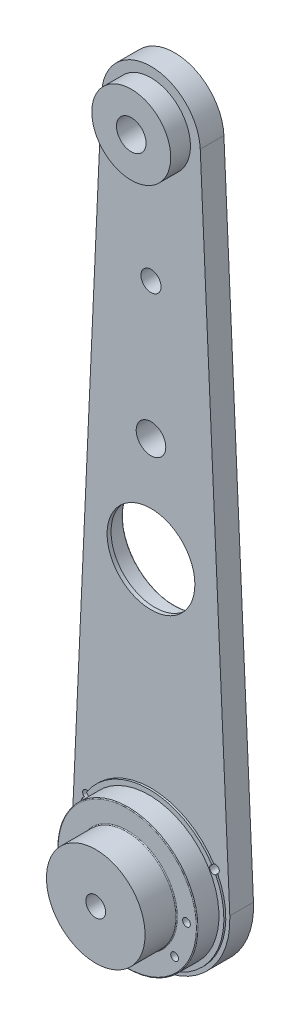
SolidWorks part; units mm, degrees
ref_plane "Front Plane" through (0, 0, 0) normal (0, 0, 1) x (1, 0, 0)
ref_plane "Top Plane" through (0, 0, 0) normal (0, 1, 0) x (1, 0, 0)
ref_plane "Right Plane" through (0, 0, 0) normal (1, 0, 0) x (0, 0, -1)
sketch "Sketch1" plane through (0, 0, 0) normal (0, 0, 1) x (1, 0, 0)
  line L0 (0, 209.417) -> (0, 0) construction
  line L1 (25.3737, 1.1553) -> (15.8586, 210.1391)
  line L2 (-15.8586, 210.1391) -> (-25.3737, 1.1553)
  circle A1 centre (0, 209.417) radius 4.7625
  arc A2 (-15.8586, 210.1391) -> (15.8586, 210.1391) centre (0, 209.417) cw
  arc A3 (-25.3737, 1.1553) -> (25.3737, 1.1553) centre (0, 0) ccw
  dimension "D2" = 15.875
  dimension "D3" = 25.4
  dimension "D4" = 9.525
  dimension "D1" = 209.417
extrude "Boss-Extrude1" add sketch "Sketch1" along normal mid plane 7.62
sketch "Sketch2" plane through (0, 0, 3.81) normal (0, 0, 1) x (1, 0, 0)
  circle A0 centre (0, 0) radius 22.5
  dimension "D1" = 45
extrude "Boss-Extrude2" add sketch "Sketch2" along normal blind 7.62
sketch "Sketch3" plane through (0, 0, 3.81) normal (0, 0, 1) x (1, 0, 0)
  circle A0 centre (0, 0) radius 24.0899
extrude "Boss-Extrude3" add sketch "Sketch3" along normal offset from surface (0.62 mm away) 7 up to face at (22.5, 0, 11.43)
sketch "Sketch4" plane through (0, 0, 3.81) normal (0, 0, 1) x (1, 0, 0)
  circle A0 centre (0, 87.917) radius 16.6687
  circle A1 centre (0, 121.5) radius 4.7625
  circle A2 centre (0, 209.417) radius 4.7625 construction
  dimension "D2" = 33.3375
  dimension "D3" = 9.525
  dimension "D1" = 87.917
  dimension "D4" = 87.917
extrude "Cut-Extrude1" cut sketch "Sketch4" against normal through all both and the other way through all
sketch "Sketch6" plane through (0, 0, 3.81) normal (0, 0, 1) x (1, 0, 0)
  circle A0 centre (0, 87.917) radius 16.6687
  circle A1 centre (0, 87.917) radius 14.1288
  circle A2 centre (0, 87.917) radius 16.6687 construction
  dimension "D1" = 2.54
extrude "Boss-Extrude4" add sketch "Sketch6" against normal offset from surface (1.27 mm away) 6.35 up to face at (16.6687, 87.917, -3.81)
sketch "Sketch5" plane through (0, 0, 0) normal (0, 0, 1) x (1, 0, 0)
  line L0 (-155.5635, 76.3042) -> (0, 231.8677)
  line L1 (-155.5635, 76.3042) -> (0, -79.2593)
  line L2 (0, 231.8677) -> (155.5635, 76.3042)
  line L3 (0, -79.2593) -> (155.5635, 76.3042)
  line L4 (-155.5635, 76.3042) -> (155.5635, 76.3042) construction
  line L5 (0, 231.8677) -> (0, -79.2593) construction
  arc A1 (15.8586, 210.1391) -> (-15.8586, 210.1391) centre (0, 209.417) ccw construction
  point P1 (0, 76.3042)
  dimension "D1" = 220
sketch "Sketch7" plane through (0, 0, -3.81) normal (0, 0, -1) x (-1, 0, 0)
  line L1 (-11.7937, -8.3562) -> (-11.7937, 8.3562)
  line L2 (11.7937, -8.3562) -> (11.7937, 8.3562)
  line L3 (-11.7937, 8.3562) -> (11.7937, 8.3562)
  line L4 (-11.7937, -8.3562) -> (11.7937, 8.3562) construction
  line L5 (11.7937, -8.3562) -> (-11.7937, 8.3562) construction
  line L6 (-11, 7.5625) -> (-11.7937, 8.3562) construction
  line L7 (11.7937, 8.3562) -> (11, 7.5625) construction
  line L8 (-11.7937, -8.3562) -> (-11.7937, -22.4959)
  line L10 (11.7937, -22.4959) -> (11.7937, -8.3562)
  line L11 (-11, 7.5625) -> (-11, -20.6542) construction
  arc A0 (-11.7937, -22.4959) -> (11.7937, -22.4959) centre (0, 0) ccw
  arc A1 (-25.3737, 1.1553) -> (25.3737, 1.1553) centre (0, 0) ccw construction
  point P0 (11, 7.5625)
  point P1 (0, 0)
  point P2 (-11, 7.5625)
  point P11 (11, -20.6542)
  dimension "D1" = 0.7937
extrude "Cut-Extrude2" cut sketch "Sketch7" against normal blind 2.54
sketch "Sketch8" plane through (0, 0, -1.27) normal (0, 0, -1) x (-1, 0, 0)
  circle A0 centre (9, -5.5625) radius 0.95
  circle A1 centre (-9, -5.5625) radius 0.95
  circle A2 centre (-9, 5.5625) radius 0.95
  circle A3 centre (9, 5.5625) radius 0.95
  dimension "D1" = 1.9
extrude "Cut-Extrude3" cut sketch "Sketch8" against normal through all
sketch "Sketch9" plane through (0, 0, 3.81) normal (0, 0, 1) x (1, 0, 0)
  circle A0 centre (0, 209.417) radius 12.7
  circle A1 centre (0, 209.417) radius 4.7625 construction
  circle A2 centre (0, 209.417) radius 4.7625
  dimension "D1" = 25.4
extrude "Boss-Extrude5" add sketch "Sketch9" along normal blind 6.35
sketch "Sketch10" plane through (0, 0, 11.43) normal (0, 0, 1) x (1, 0, 0)
  circle A0 centre (0, 0) radius 15.875
  dimension "D1" = 31.75
extrude "Boss-Extrude6" add sketch "Sketch10" along normal blind 10.16
sketch "Sketch11" plane through (0, 0, -3.81) normal (0, 0, -1) x (-1, 0, 0)
  circle A0 centre (-20.7431, 11.983) radius 1.25
  circle A1 centre (-19.0618, 0) radius 1.25
  circle A2 centre (-15.2212, -11.4747) radius 1.25
  circle A3 centre (15.2212, -11.4747) radius 1.25
  circle A4 centre (19.0618, 0) radius 1.25
  circle A5 centre (20.7431, 11.983) radius 1.25
  dimension "D1" = 2.5
extrude "Cut-Extrude4" cut sketch "Sketch11" against normal through all both and the other way through all
sketch "Sketch12" plane through (0, 0, 3.81) normal (0, 0, 1) x (1, 0, 0)
  line L0 (0, 209.417) -> (0, 121.5) construction
  circle A8 centre (0, 165.4585) radius 3.2385
  dimension "D1" = 6.477
extrude "Cut-Extrude5" cut sketch "Sketch12" against normal through all both and the other way through all
sketch "Sketch14" plane through (0, 0, -1.27) normal (0, 0, -1) x (-1, 0, 0)
  circle A0 centre (0, 0) radius 3.175
  dimension "D1" = 6.35
extrude "Cut-Extrude6" cut sketch "Sketch14" against normal through all
sketch "Sketch15" plane through (0, 0, -1.27) normal (0, 0, -1) x (-1, 0, 0)
  circle A0 centre (0, 0) radius 6.35
  dimension "D1" = 12.7
extrude "Cut-Extrude7" cut sketch "Sketch15" against normal blind 7.62
fillet "Fillet1" radius 0.254 4 edges at (16.6687, 87.917, -3.81) (-16.6687, 87.917, 2.54) (15.875, 0, 11.43) (22.5, 0, 11.43)
equation "\"UpperLinkLength\"= \"LowerFirstStage\" + \"LowerSecondStage\""
equation "\"LowerFirstStage\"= \"60T_20T_122B\""
equation "\"LowerSecondStage\"= \"60T_20T_100B\""
equation "\"D1@Sketch1\"=\"UpperLinkLength\""
equation "\"UpperStage\"= \"60T_20T_100B\""
equation "\"60T_20T_100B\"= 3.4613"
equation "\"60T_20T_125B\"= 4.9626"
equation "\"D1@Sketch4\"=\"UpperStage\""
equation "\"D4@Sketch4\"=\"LowerSecondStage\""
equation "\"60T_20T_122B\"= 121.5mm"
